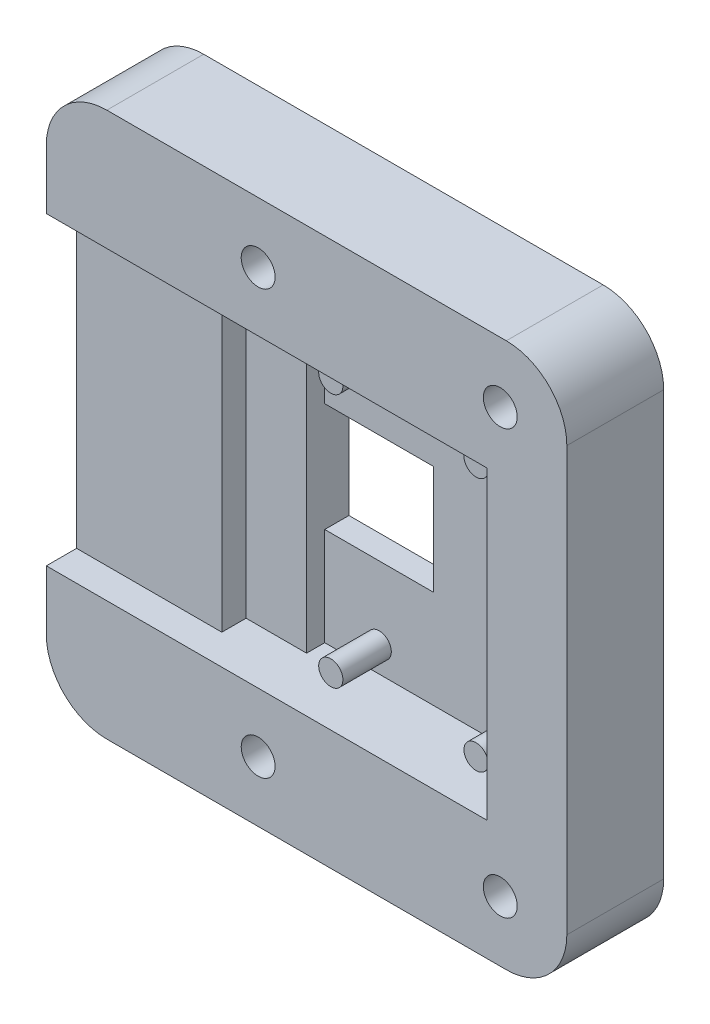
SolidWorks part; units mm, degrees
ref_plane "정면" through (0, 0, 0) normal (0, 0, 1) x (1, 0, 0)
ref_plane "윗면" through (0, 0, 0) normal (0, 1, 0) x (1, 0, 0)
ref_plane "우측면" through (0, 0, 0) normal (1, 0, 0) x (0, 0, -1)
sketch "스케치1" plane through (0, 0, 0) normal (0, 0, 1) x (1, 0, 0)
  line L0 (0, 0) -> (0, 22.5) construction
  line L1 (-15.5, 22.5) -> (15.5, 22.5)
  line L2 (-15.5, 22.5) -> (-15.5, -22.5) construction
  line L3 (-15.5, -22.5) -> (15.5, -22.5)
  line L4 (15.5, 22.5) -> (15.5, -22.5)
  line L5 (-15.5, 22.5) -> (15.5, -22.5) construction
  line L6 (-15.5, -22.5) -> (15.5, 22.5) construction
  line L7 (0, 0) -> (-15.5, 0) construction
  line L8 (-6, 0) -> (-6, 10.5) construction
  line L13 (-10.5, 4.5) -> (-1.5, 4.5)
  line L14 (-10.5, 4.5) -> (-10.5, -4.5)
  line L15 (-10.5, -4.5) -> (-1.5, -4.5)
  line L16 (-1.5, 4.5) -> (-1.5, -4.5)
  line L17 (-10.5, 4.5) -> (-1.5, -4.5) construction
  line L18 (-10.5, -4.5) -> (-1.5, 4.5) construction
  line L19 (-15.5, 22.5) -> (-27.5, 22.5)
  line L20 (-27.5, 22.5) -> (-27.5, -22.5)
  line L21 (-27.5, -22.5) -> (-15.5, -22.5)
  circle A0 centre (-6, 10.5) radius 1
  circle A1 centre (6, 10.5) radius 1
  circle A2 centre (6, -10.5) radius 1
  circle A3 centre (-6, -10.5) radius 1
  point P0 (0, 0)
  point P10 (0, 0)
  point P22 (-6, 0)
  dimension "D1" = 2
  dimension "D2" = 12
  dimension "D3" = 21
  dimension "D4" = 9
  dimension "D5" = 9
  dimension "D6" = 5
  dimension "D7" = 45
  dimension "D8" = 21.5
extrude "보스-돌출1" add sketch "스케치1" along normal blind 2 contours L2 L3 L4 L1 A1 A0 A2 A3 region at (0, 21.8776, 0)
sketch "스케치3" plane through (0, 0, 2) normal (0, 0, 1) x (1, 0, 0)
  line L0 (-10.5, 4.5) -> (-10.5, -4.5) construction
  line L2 (-27.5, 22.5) -> (-10.5, 22.5)
  line L3 (-27.5, 22.5) -> (-27.5, -22.5)
  line L4 (-27.5, -22.5) -> (-10.5, -22.5)
  line L5 (-10.5, 22.5) -> (-10.5, -22.5)
  line L6 (-27.5, 22.5) -> (-10.5, -22.5) construction
  line L7 (-27.5, -22.5) -> (-10.5, 22.5) construction
  line L9 (-27.5, -22.5) -> (15.5, -22.5) construction
  line L10 (-27.5, 22.5) -> (15.5, 22.5) construction
  line L11 (-27.5, 22.5) -> (-27.5, -22.5) construction
  point P0 (-19, 0)
  point P7 (-19.8956, -4.0583)
  point P10 (-10.5, -6.2467)
  point P11 (-10.5, -19.6681)
  point P14 (-10.5, 19.6681)
extrude "보스-돌출3" add sketch "스케치3" along normal blind 1.5
sketch "스케치4" plane through (0, 0, 2) normal (0, 0, 1) x (1, 0, 0)
  line L1 (-15.5, -22.5) -> (15.5, -22.5)
  line L2 (-15.5, -22.5) -> (-15.5, -12.6) construction
  line L3 (-15.5, 22.5) -> (15.5, 22.5)
  line L4 (15.5, -22.5) -> (15.5, 22.5)
  line L5 (-15.5, -22.5) -> (15.5, 22.5) construction
  line L6 (-15.5, 22.5) -> (15.5, -22.5) construction
  line L7 (8.9, 12.6) -> (8.9, -12.6)
  line L8 (8.9, -12.6) -> (-15.5, -12.6)
  line L10 (0, 0) -> (15.5, 0) construction
  line L11 (-15.5, 22.5) -> (-15.5, 12.6) construction
  line L12 (8.9, 12.6) -> (-15.5, 12.6)
  line L14 (-1.5, 4.5) -> (-1.5, -4.5) construction
  line L16 (-10.5, 22.5) -> (15.5, 22.5) construction
  line L17 (15.5, 22.5) -> (15.5, -22.5) construction
  line L18 (-15.5, 22.5) -> (-27.5, 22.5)
  line L19 (-27.5, 22.5) -> (-27.5, 12.6)
  line L20 (-27.5, 22.5) -> (-27.5, -22.5) construction
  line L21 (-27.5, 12.6) -> (-15.5, 12.6)
  line L22 (-15.5, -22.5) -> (-27.5, -22.5)
  line L23 (-27.5, -22.5) -> (-27.5, -12.6)
  line L24 (-27.5, -12.6) -> (-15.5, -12.6)
  point P0 (0, 0)
  point P14 (8.9, 0)
  point P27 (-27.5, 22.5)
  dimension "D1" = 25.2
  dimension "D2" = 10.4
extrude "보스-돌출4" add sketch "스케치4" along normal blind 6
extrude "보스-돌출5" add sketch "스케치1<3>" along normal blind 6 contours A0 | A1 | A3 | A2 region at (-6, 10.5, 0) region at (6, 10.5, 0) region at (6, -10.5, 0) region at (-6, -10.5, 0)
sketch "스케치1<3>" plane through (0, 0, 0) normal (0, 0, 1) x (1, 0, 0) same geometry as "스케치1"
sketch "스케치6" plane through (0, 0, 0) normal (0, 0, 1) x (1, 0, 0)
  line L0 (0, 0) -> (-20, 0) construction
  line L1 (0, 0) -> (0, 30) construction
  line L2 (-6, -4.5) -> (-6, 4.5) construction
  line L3 (-10.5, -4.5) -> (-1.5, -4.5) construction
  line L4 (-10.5, 4.5) -> (-1.5, 4.5) construction
  circle A0 centre (-10, 17.5) radius 1.4
  circle A1 centre (10, 17.5) radius 1.4
  circle A2 centre (10, -17.5) radius 1.4
  circle A3 centre (-10, -17.5) radius 1.4
  dimension "D3" = 2.8
  dimension "D1" = 20
  dimension "D2" = 30
  dimension "D4" = 20
  dimension "D5" = 35
extrude "컷-돌출1" cut sketch "스케치6" along normal through all
chamfer "모따기1" distance 2 angle 45 4 edges at (8.6, 17.5, 0) (-8.6, 17.5, 0) (-11.4, -17.5, 0) (11.4, -17.5, 0)
sketch "스케치7" plane through (0, 0, 3.5) normal (0, 0, 1) x (1, 0, 0)
  line L0 (8.9, -12.6) -> (-27.5, -12.6) construction
  line L1 (-27.5, 12.6) -> (-15.5, 12.6)
  line L2 (-27.5, 12.6) -> (-27.5, -12.6)
  line L3 (-27.5, -12.6) -> (-15.5, -12.6)
  line L4 (-15.5, 12.6) -> (-15.5, -12.6)
  line L5 (-10.5, -12.6) -> (-10.5, 12.6) construction
  dimension "D1" = 5
extrude "보스-돌출6" add sketch "스케치7" along normal blind 2
fillet "필렛1" radius 5 4 edges at (15.5, -22.5, 4) (15.5, 22.5, 4) (-27.5, 22.5, 4) (-27.5, -22.5, 4)
